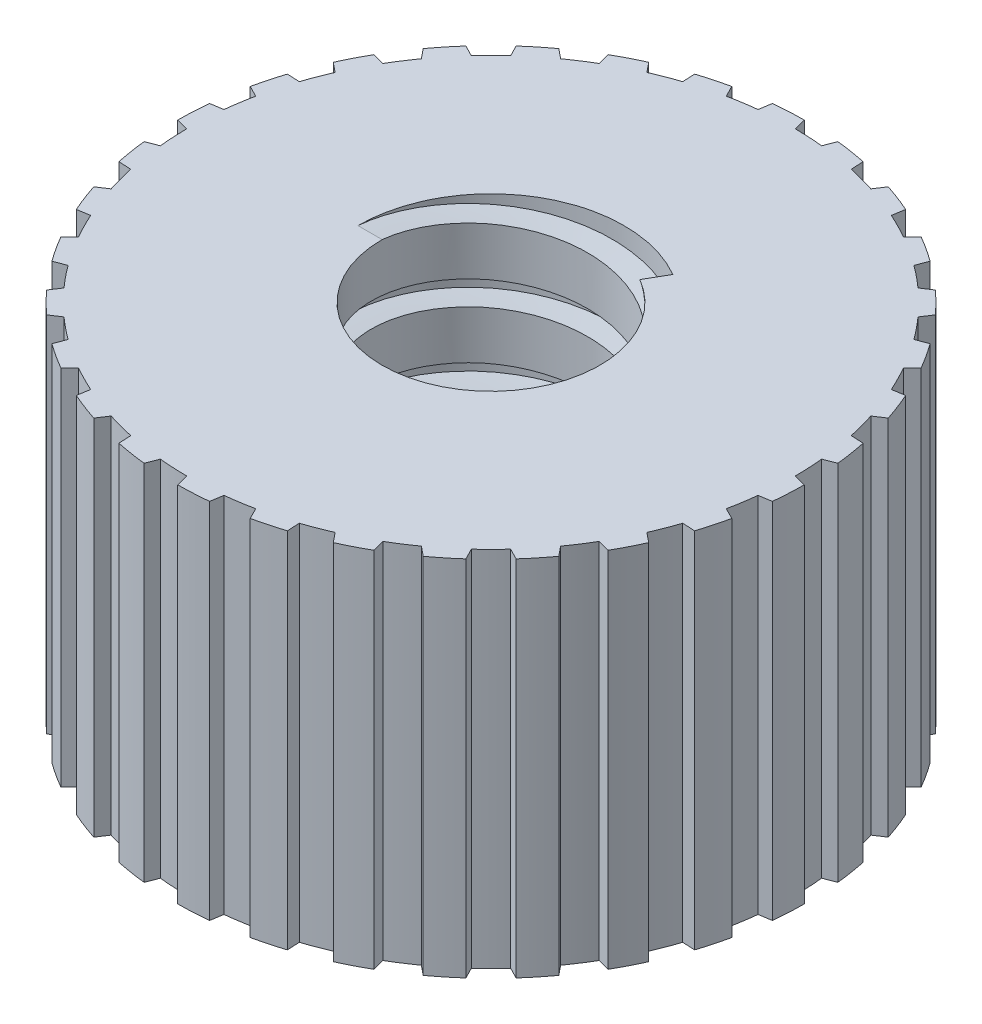
SolidWorks part; units mm, degrees
ref_plane "Front Plane" through (0, 0, 0) normal (0, 0, 1) x (1, 0, 0)
ref_plane "Top Plane" through (0, 0, 0) normal (0, 1, 0) x (1, 0, 0)
ref_plane "Right Plane" through (0, 0, 0) normal (1, 0, 0) x (0, 0, -1)
sketch "Sketch1" plane through (0, 0, 0) normal (0, 1, 0) x (1, 0, 0)
  circle A0 centre (0, 0) radius 13
  circle A1 centre (0, 0) radius 4.5
  dimension "D1" = 26
  dimension "D2" = 9
extrude "Boss-Extrude1" add sketch "Sketch1" along normal blind 15
sketch "Sketch6" plane through (0, 0, 0) normal (0, -1, 0) x (1, 0, 0)
  circle A0 centre (0, 0) radius 4.5 construction
  circle A1 centre (0, 0) radius 4.5
curve "Helix/Spiral2" pitch 3 height 15 turns 5
sketch "Sketch7" plane through (0, 0, 0) normal (0, 0, 1) x (1, 0, 0)
  line L0 (-4.5, 0) -> (-4.5, 1)
  line L1 (-4.5, 1) -> (-5.5, 1)
  line L2 (-5.5, 1) -> (-5.5, 0)
  line L3 (-13, 0) -> (13, 0) construction
  line L4 (-5.5, 0) -> (-4.5, 0)
  dimension "D1" = 1
  dimension "D2" = 1
sweep "Cut-Sweep1" cut profiles "Sketch7" path "Helix/Spiral2" align with end faces yes
sketch "Sketch8" plane through (0, 15, 0) normal (0, 1, 0) x (1, 0, 0)
  line L6 (0, 12.8) -> (0, 0) construction
  line L7 (0, 0) -> (1.338, 12.7299) construction
  line L8 (0.0805, 12.4997) -> (-0.1872, 13.4987)
  line L10 (1.2266, 12.4397) -> (1.5972, 13.4052)
  arc A1 (1.5972, 13.4052) -> (-0.1872, 13.4987) centre (0, 0) ccw
  arc A3 (1.2266, 12.4397) -> (0.0805, 12.4997) centre (0, 0) ccw
  arc A4 (1.338, 12.7299) -> (0, 12.8) centre (0, 0) ccw construction
  point P1 (0, 0)
  point P7 (-0.2194, 13.4982)
  point P10 (1.7575, 13.3851)
  point P77 (0, 0)
  dimension "D5" = 25.6
  dimension "D3" = 6
  dimension "D1" = 13.5
  dimension "D2" = 12.5
  dimension "D4" = 15
  dimension "D6" = 15
extrude "Cut-Extrude2" cut sketch "Sketch8" against normal through all
pattern_circular "CirPattern1" count 30 over 360 about axis through (0, 0, 0) along (0, 1, 0) of "Cut-Extrude2"
